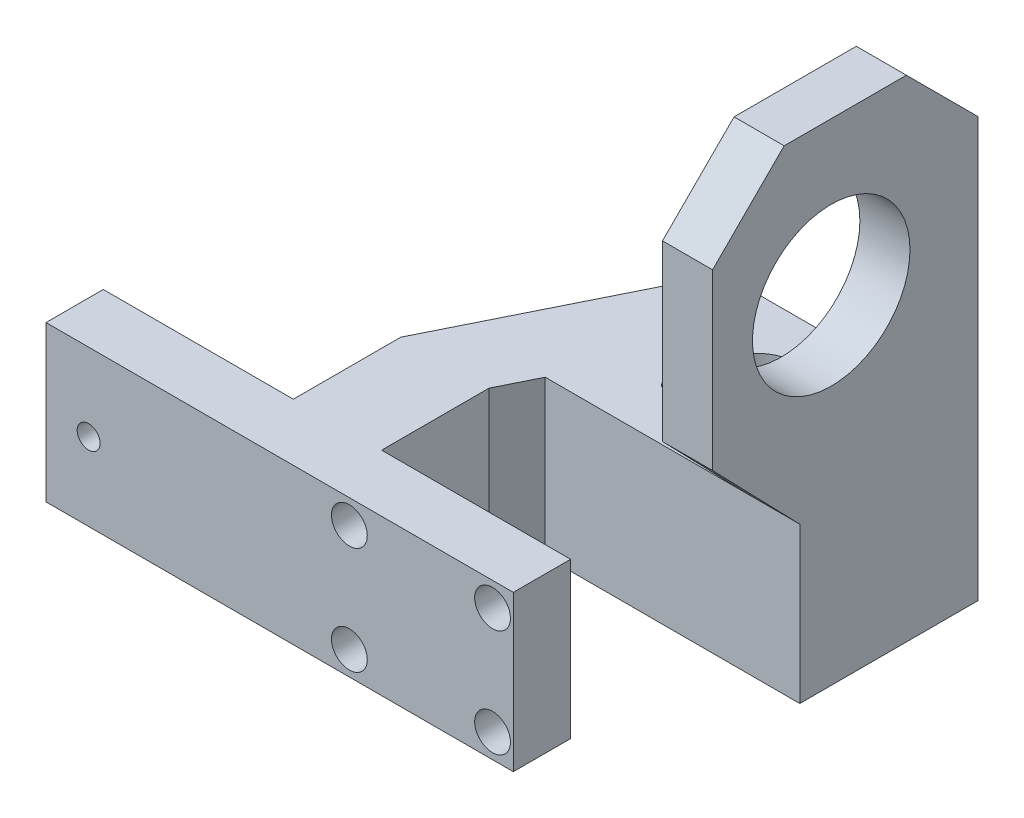
SolidWorks part; units mm, degrees
ref_plane "Přední rovina" through (0, 0, 0) normal (0, 0, 1) x (1, 0, 0)
ref_plane "Horní rovina" through (0, 0, 0) normal (0, 1, 0) x (1, 0, 0)
ref_plane "Pravá rovina" through (0, 0, 0) normal (1, 0, 0) x (0, 0, -1)
sketch "Skica1" plane through (0, 0, 0) normal (0, 0, 1) x (1, 0, 0)
  line L1 (16.212, -19.9414) -> (-34.0669, -19.9414)
  line L2 (16.212, -19.9414) -> (16.212, 1.7586)
  line L3 (16.212, 1.7586) -> (-34.0669, 1.7586)
  line L4 (-34.0669, -19.9414) -> (-34.0669, 1.7586)
  circle A0 centre (13.312, -16.5914) radius 1.6
  circle A1 centre (-6.688, -16.5914) radius 1.6
  circle A2 centre (-6.688, -1.5914) radius 1.6
  circle A3 centre (13.312, -1.5914) radius 1.6
  dimension "D1" = 3.2
  dimension "D2" = 2
  dimension "D3" = 2
extrude "Přidat vysunutím1" add sketch "Skica1" along normal blind 8
sketch "Skica2" plane through (0, 0, 8) normal (0, 0, 1) x (1, 0, 0)
  circle A0 centre (13.312, -16.5914) radius 2.5
  circle A1 centre (-6.688, -16.5914) radius 2.5
  circle A2 centre (-6.688, -1.5914) radius 2.5
  circle A3 centre (13.312, -1.5914) radius 2.5
  dimension "D1" = 5
  dimension "D2" = 2
  dimension "D3" = 2
extrude "Odebrat vysunutím1" cut sketch "Skica2" against normal blind 4
sketch "Skica4" plane through (0, 0, 0) normal (0, 0, -1) x (-1, 0, 0)
  line L0 (-16.212, 1.7586) -> (34.0669, 1.7586) construction
  line L1 (10.188, 1.7586) -> (22.5157, 1.7586)
  line L2 (10.188, 1.7586) -> (10.188, -19.9414)
  line L3 (10.188, -19.9414) -> (22.5157, -19.9414)
  line L4 (22.5157, 1.7586) -> (22.5157, -19.9414)
  line L5 (10.188, 1.7586) -> (10.188, -19.9414) construction
  line L6 (34.0669, -19.9414) -> (-16.212, -19.9414) construction
  line L7 (10.188, -19.9414) -> (10.188, 1.7586) construction
extrude "Přidat vysunutím2" add sketch "Skica4" along normal blind 15
sketch "Skica6" plane through (0, 1.7586, 0) normal (0, 1, 0) x (1, 0, 0)
  line L0 (-10.188, 15) -> (-22.5157, 15)
  line L1 (-10.188, 15) -> (-7.5858, 20.255)
  line L2 (-22.5157, 15) -> (-7.5858, 45.15)
  line L3 (4.7419, 45.15) -> (-7.5858, 45.15)
  line L5 (-7.5858, 45.15) -> (20.9737, 45.15)
  line L7 (-7.5858, 20.255) -> (20.9737, 20.255)
  line L8 (20.9737, 45.15) -> (20.9737, 20.255)
  circle A0 centre (8.2082, 34.15) radius 11 construction
  circle A3 centre (8.2082, 34.15) radius 5.4063
  line M11 (-10.188, 15) -> (-22.5157, 15)
extrude "Přidat vysunutím3" add sketch "Skica6" against normal up to surface (21.7 mm away) contours L8 L5 L3 L2 L1 L7 A3 M11 region at (1.476, 1.7586, -30.6172) up to face at (-12.6397, -19.9414, -1.75)
sketch "Skica7" plane through (0, -19.9414, 0) normal (0, -1, 0) x (1, 0, 0)
  line L0 (8.2082, -34.15) -> (0.2082, -34.15) construction
  line L1 (8.2082, -34.15) -> (2.5514, -28.4931) construction
  line L2 (8.2082, -34.15) -> (13.8651, -39.8069) construction
  circle A0 centre (8.2082, -34.15) radius 8 construction
  circle A1 centre (2.5514, -28.4931) radius 1.5
  circle A2 centre (13.8651, -39.8069) radius 1.5
  point P12 (8.2082, -34.15)
  dimension "D1" = 16
  dimension "D2" = 3
  dimension "D3" = 2
extrude "Odebrat vysunutím3" cut sketch "Skica7" against normal up to surface (21.7 mm away) up to face at (-6.1951, 1.7586, -12.0675)
sketch "Skica8" plane through (-34.0669, 0, 0) normal (-1, 0, 0) x (0, 0, 1)
  line L4 (0, 1.7586) -> (0, -19.9414)
  line L5 (0, -19.9414) -> (8, -19.9414)
  line L6 (8, -19.9414) -> (8, 1.7586)
  line L7 (8, 1.7586) -> (0, 1.7586)
  line L8 (0, 1.7586) -> (0, -19.9414)
  line L9 (0, -19.9414) -> (8, -19.9414)
  line L10 (8, -19.9414) -> (8, 1.7586)
  line L11 (8, 1.7586) -> (0, 1.7586)
  dimension "D1" = 0
extrude "Přidat vysunutím4" add sketch "Skica8" along normal blind 15
sketch "Skica9" plane through (0, 0, 8) normal (0, 0, 1) x (1, 0, 0)
  circle A0 centre (-43.1091, -9.0914) radius 1.6
  circle A1 centre (-243.1091, -9.0914) radius 1.6 construction
extrude "Odebrat vysunutím4" cut sketch "Skica9" against normal blind 15
sketch "Skica10" plane through (20.9737, 0, 0) normal (1, 0, 0) x (0, 0, -1)
  line L0 (8.0742, 14.3404) -> (20.255, 1.7586)
  line L1 (45.15, -19.9414) -> (20.255, -19.9414)
  line L2 (45.15, -19.9414) -> (45.15, 48.6222)
  line L3 (45.15, 48.6222) -> (8.0742, 48.6222)
  line L4 (8.0742, 14.3404) -> (8.0742, 48.6222)
  line L5 (20.255, 1.7586) -> (20.255, -19.9414)
  circle A0 centre (24.65, 27.2586) radius 11
  dimension "D1" = 22
extrude "Přidat vysunutím5" add sketch "Skica10" along normal blind 7
chamfer "Zkosení1" distance 10 angle 45 2 edges at (24.4737, 48.6222, -8.0742) (24.4737, 48.6222, -45.15)
